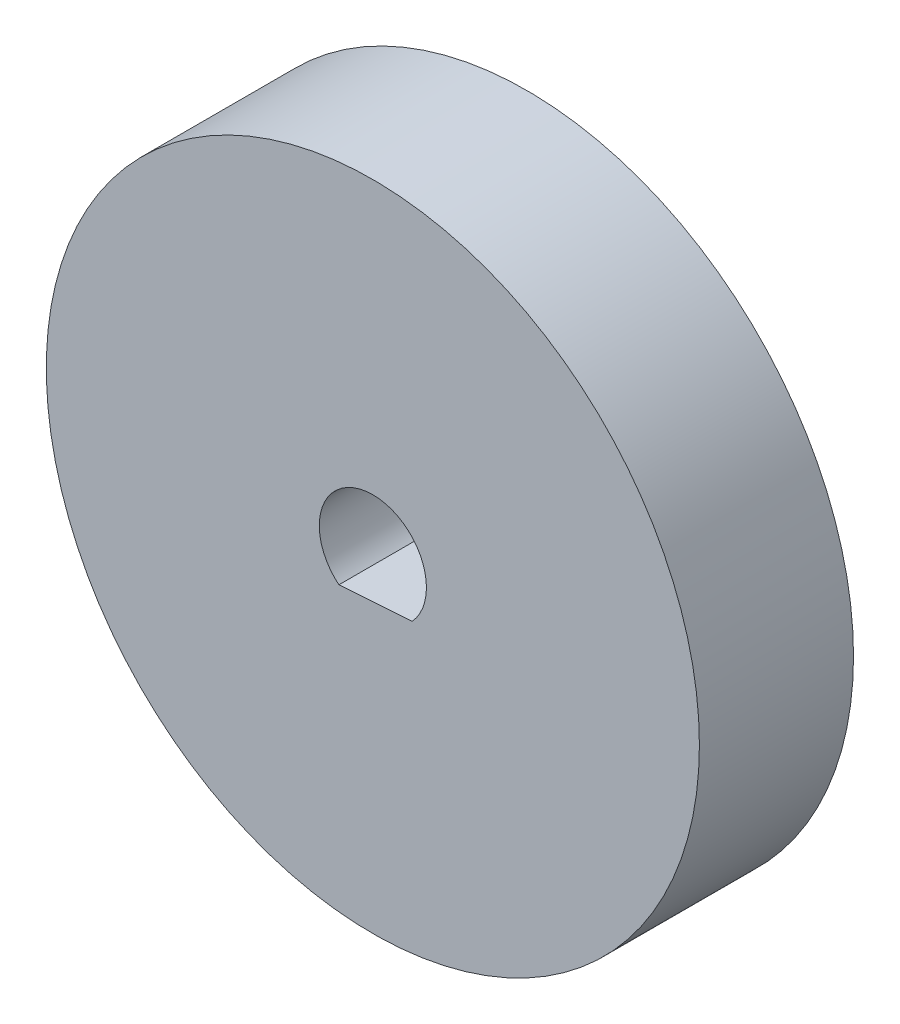
SolidWorks part; units mm, degrees
ref_plane "Front Plane" through (0, 0, 0) normal (0, 0, 1) x (1, 0, 0)
ref_plane "Top Plane" through (0, 0, 0) normal (0, 1, 0) x (1, 0, 0)
ref_plane "Right Plane" through (0, 0, 0) normal (1, 0, 0) x (0, 0, -1)
sketch "Sketch1" plane through (0, 0, 0) normal (0, 0, 1) x (1, 0, 0)
  circle A0 centre (0, 7.2896) radius 11.303
  dimension "D1" = 22.606
extrude "Boss-Extrude1" add sketch "Sketch1" along normal blind 5.334
sketch "Sketch2" plane through (0, 0, 0) normal (0, 0, -1) x (-1, 0, 0)
  line L1 (-1.361, 6.0304) -> (1.175, 5.8552)
  circle A0 centre (0, 7.2896) radius 1.8542
  circle A1 centre (0, 7.2896) radius 11.303 construction
  dimension "D1" = 3.7084
  dimension "D3" = 0
  dimension "D2" = 1.35
extrude "Cut-Extrude1" cut sketch "Sketch2" against normal through all contours L1 A0 region at (-0.0095, 7.4273, 0)
equation "\"MDF\"= .21in"
equation "\"Foamcore\"= .13in"
equation "\"Gmaterial\"= \"MDF\""
equation "\"D1@Boss-Extrude1\"=\"MDF\""
